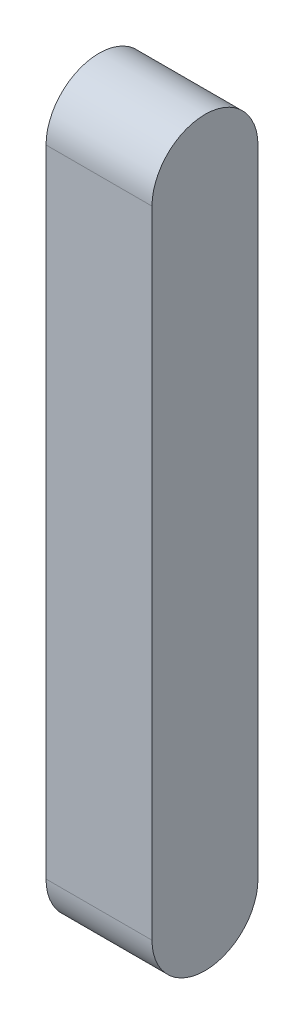
SolidWorks part; units mm, degrees
ref_plane "前视基准面" through (0, 0, 0) normal (0, 0, 1) x (1, 0, 0)
ref_plane "上视基准面" through (0, 0, 0) normal (0, 1, 0) x (1, 0, 0)
ref_plane "右视基准面" through (0, 0, 0) normal (1, 0, 0) x (0, 0, -1)
sketch "草图1" plane through (0, 0, 0) normal (1, 0, 0) x (0, 0, -1)
  line L1 (-5, 30) -> (5, 30)
  line L2 (-5, 30) -> (-5, -30)
  line L3 (-5, -30) -> (5, -30)
  line L4 (5, 30) -> (5, -30)
  line L5 (-5, 30) -> (5, -30) construction
  line L6 (-5, -30) -> (5, 30) construction
  circle A0 centre (0, 30) radius 5
  circle A1 centre (0, -30) radius 5
  point P0 (0, 0)
extrude "凸台-拉伸1" add sketch "草图1" along normal blind 10 contours L4 L3 L2 L1 | A1 | A0
